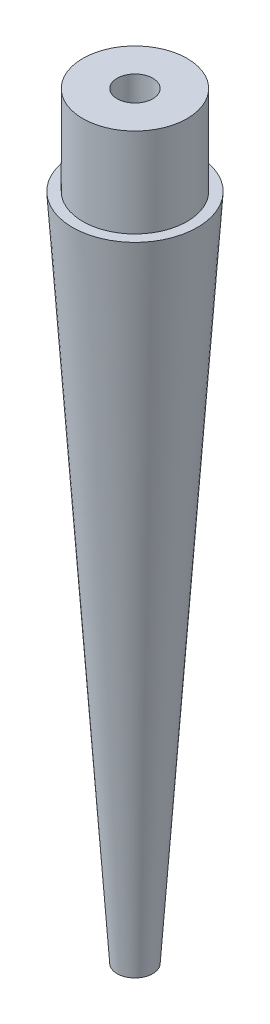
SolidWorks part; units mm, degrees
ref_plane "Front Plane" through (0, 0, 0) normal (0, 0, 1) x (1, 0, 0)
ref_plane "Top Plane" through (0, 0, 0) normal (0, 1, 0) x (1, 0, 0)
ref_plane "Right Plane" through (0, 0, 0) normal (1, 0, 0) x (0, 0, -1)
sketch "Sketch1" plane through (0, 0, 0) normal (0, 1, 0) x (1, 0, 0)
  circle A0 centre (0, 0) radius 7
  circle A1 centre (0, 0) radius 5.85
  circle A2 centre (0, 0) radius 2
  dimension "D1" = 11.7
  dimension "D2" = 14
  dimension "D3" = 4
sketch "Sketch2" plane through (0, 0, 0) normal (1, 0, 0) x (0, 0, -1)
  line L0 (7, 0) -> (-7, 0) construction
  line L1 (7, 0) -> (-7, 0)
  line L2 (0, 0) -> (0, -105) construction
  line L3 (7, 0) -> (0, -105)
  line L4 (0, -105) -> (0, 0)
  line L5 (0, 0) -> (7, 0)
  dimension "D1" = 105
revolve "Revolve1" add sketch "Sketch2" angle 360 about L2 region at (0, -35, -2.3333)
extrude "Boss-Extrude1" add sketch "Sketch1" along normal blind 10 contours A1
extrude "Cut-Extrude1" cut sketch "Sketch1<4>" against normal through all both and the other way through all contours A2
sketch "Sketch1<4>" plane through (0, 0, 0) normal (0, 1, 0) x (1, 0, 0) same geometry as "Sketch1"
